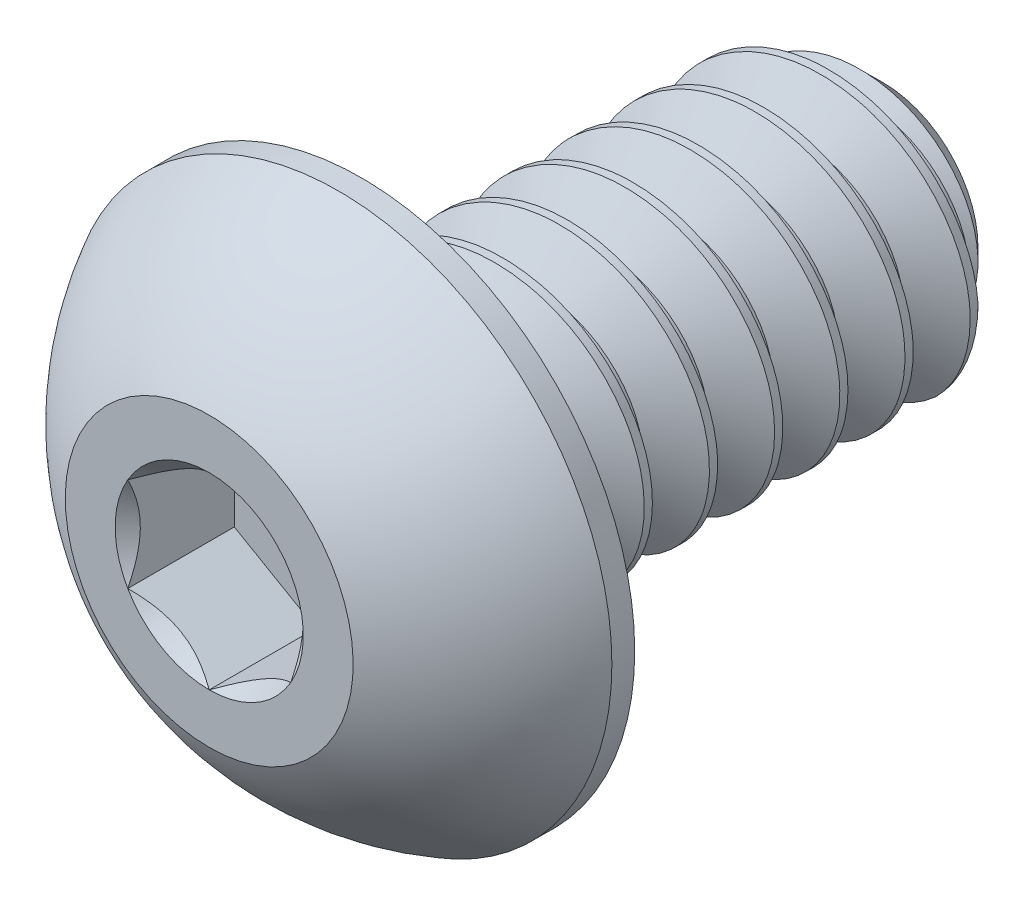
SolidWorks part; units mm, degrees
material "AISI 316 Annealed Stainless Steel Bar (SS)"
ref_plane "Front" through (0, 0, 0) normal (0, 0, 1) x (1, 0, 0)
ref_plane "Top" through (0, 0, 0) normal (0, 1, 0) x (1, 0, 0)
ref_plane "Right" through (0, 0, 0) normal (1, 0, 0) x (0, 0, -1)
sketch "Sketch1" plane through (0, 0, 0) normal (1, 0, 0) x (0, 0, -1)
  line L2 (1.8542, 1.7526) -> (8.2042, 1.7526)
  line L3 (8.2042, 1.7526) -> (8.2042, 0)
  line L4 (8.2042, 0) -> (1.8542, 0)
  line L6 (1.5761, 3.3274) -> (1.8542, 3.3274) construction
  line L7 (8.2042, 1.7526) -> (8.2042, -1.7526) construction
  line L8 (0, 0) -> (1.8542, 0) construction
  line L9 (1.8542, 3.3274) -> (1.8542, -3.3274) construction
  line L11 (1.8542, 1.7526) -> (1.8542, 0)
  line L13 (0, 0.9922) -> (0, -0.9922) construction
  line L14 (0, 0.9922) -> (0, 1.7526) construction
  arc A3 (0, 1.7526) -> (1.5761, 3.3274) centre (3.326, 0) cw construction
  dimension "D1" = 0.2781
revolve "Revolve1" add sketch "Sketch1" angle 360 mid plane about L4
sketch "Sketch3" plane through (0, 0, -8.2042) normal (0, 0, -1) x (-1, 0, 0)
  circle A0 centre (0, 0) radius 1.7526
curve "Helix/Spiral1" pitch 0.7937 height 7.1437 radius 1.7526 centre (0, 0, -8.2042) axis (0, 0, 1) start towards (0, 1, 0)
sketch "Sketch2" plane through (0, 0, 0) normal (1, 0, 0) x (0, 0, -1)
  line L0 (8.2042, 1.7526) -> (8.8987, 1.7526)
  line L1 (8.8987, 1.7526) -> (8.6011, 1.237)
  line L2 (8.6011, 1.237) -> (8.5019, 1.237)
  line L3 (8.5019, 1.237) -> (8.2042, 1.7526)
  line L4 (8.353, 1.4948) -> (8.7499, 1.4948) construction
  dimension "D1" = 60
  dimension "D2" = 0.0992
  dimension "D3" = 0.3969
chamfer "Chamfer1" distance 0.5953 angle 45 1 edges at (0, 1.7526, -8.2042)
sweep "Cut-Sweep1" cut profiles "Sketch2" path "Helix/Spiral1" align with end faces yes
sketch "Sketch7" plane through (0, 0, 0) normal (1, 0, 0) x (0, 0, -1)
  line L6 (1.5761, 3.3274) -> (1.8542, 3.3274) construction
  line L8 (0, 0) -> (1.8542, 0) construction
  line L11 (1.8542, 3.3274) -> (1.8542, -3.3274) construction
  line L12 (1.5761, 3.3274) -> (1.8542, 3.3274)
  line L13 (0, 0) -> (1.8542, 0)
  line L14 (0, 0.9922) -> (0, -0.9922) construction
  line L15 (1.8542, 3.3274) -> (1.8542, 0)
  line L16 (0, 1.7526) -> (0, 0)
  arc A2 (1.5761, 3.3274) -> (0, 1.7526) centre (3.326, 0) ccw construction
  arc A3 (1.5761, 3.3274) -> (0, 1.7526) centre (3.326, 0) ccw
revolve "Revolve2" add sketch "Sketch7" angle 360 mid plane about L13
sketch "Sketch5" plane through (0, 0, 0) normal (0, 0, 1) x (1, 0, 0)
  line L1 (0.9922, -0.5728) -> (0.9922, 0.5728)
  line L2 (0.9922, 0.5728) -> (0, 1.1457)
  line L3 (0, 1.1457) -> (-0.9922, 0.5728)
  line L4 (-0.9922, 0.5728) -> (-0.9922, -0.5728)
  line L5 (-0.9922, -0.5728) -> (0, -1.1457)
  line L6 (0, -1.1457) -> (0.9922, -0.5728)
  circle A0 centre (0, 0) radius 0.9922 construction
extrude "Cut-Extrude2" cut sketch "Sketch5" against normal blind 1.2979
sketch "Sketch6" plane through (0, 0, 0) normal (0, 0, 1) x (1, 0, 0)
  circle A0 centre (0, 0) radius 1.1457
extrude "Cut-Extrude3" cut sketch "Sketch6" against normal blind 1.2979 draft 45
sketch "Sketch9" [suppressed] plane through (0, 0, -1.4986) normal (0, 0, 1) x (1, 0, 0)
  circle A2 centre (0, 0) radius 1.4224
extrude "Boss-Extrude2" [suppressed] add sketch "Sketch9" against normal offset from surface (6.35 mm away) 28.575
sketch "Sketch10" plane through (0, 0, 0) normal (1, 0, 0) x (0, 0, -1)
  line L0 (8.2042, 1.7526) -> (8.2042, -1.7526) construction
  point P0 (7.0136, -1.7526)
  dimension "D1" = 1.1906
equation "\"D3@Helix/Spiral1\" = \"Lg@Sketch1\" + \"D4@Helix/Spiral1\""
equation "\"D2@Sketch2\" = \"D4@Helix/Spiral1\" * .125"
equation "\"D3@Sketch2\" = \"D4@Helix/Spiral1\" * .5"
equation "\"D1@Chamfer1\" = \"D4@Helix/Spiral1\" * .75"
equation "\"D1@Cut-Extrude2\" = \"Head Ht@Sketch1\" * .7"
equation "\"D1@Sketch1\" = \"Head Ht@Sketch1\" * .15"
equation "\"D1@Sketch10\" = \"D4@Helix/Spiral1\" * 1.5"
equation "\"D1@Cut-Extrude3\" = \"D1@Cut-Extrude2\""
